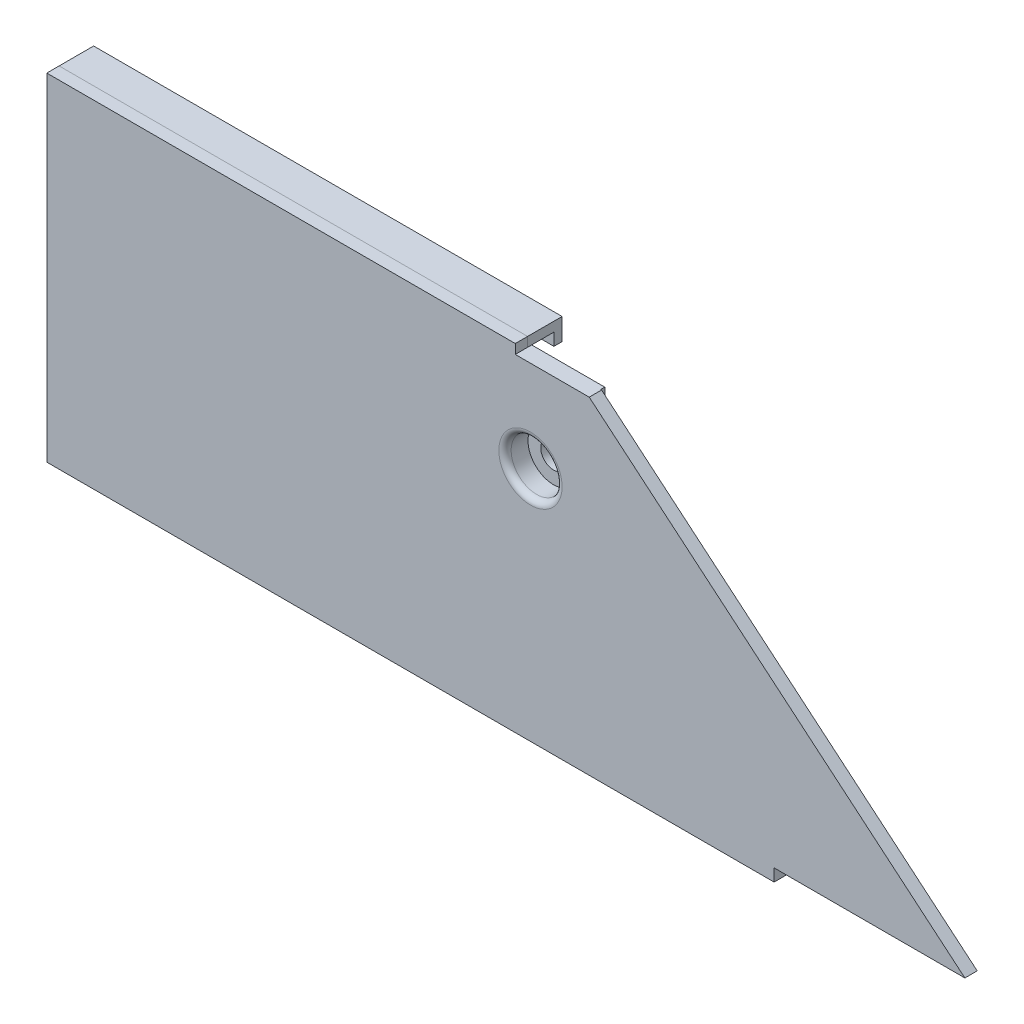
SolidWorks part; units mm, degrees
ref_plane "Спереди" through (0, 0, 0) normal (0, 0, 1) x (1, 0, 0)
ref_plane "Сверху" through (0, 0, 0) normal (0, 1, 0) x (1, 0, 0)
ref_plane "Справа" through (0, 0, 0) normal (1, 0, 0) x (0, 0, -1)
sketch "Эскиз2" plane through (0, 0, 0) normal (0, 0, 1) x (1, 0, 0)
  line L0 (-45.1615, 41.0019) -> (-45.1615, 31.0019) construction
  line L1 (-45.1615, 31.0019) -> (-100.1615, 31.0019) construction
  line L2 (-46.6615, 41.0019) -> (-46.6615, 32.1019) construction
  line L3 (-46.6615, 32.1019) -> (-100.1615, 32.1019) construction
  line L4 (-46.6615, 30.6019) -> (-45.1615, 30.6019) construction
  line L5 (-45.1615, 30.6019) -> (-45.1615, 31.0019) construction
  line L6 (-45.1615, 31.0019) -> (-46.6615, 31.0019) construction
  line L7 (-46.6615, 31.0019) -> (-46.6615, 30.6019) construction
  line L8 (-13.6668, 0) -> (13.6668, 0) construction
  line L9 (13.6668, 0) -> (-35.1974, 41.0019) construction
  line L10 (-35.1974, 41.0019) -> (-45.1615, 41.0019) construction
  line L11 (-13.6668, 0) -> (-13.6668, 1.5)
  line L12 (-13.6668, 1.5) -> (9.5456, 1.5)
  line L13 (-45.1615, 41.0019) -> (-45.1615, 39.8528)
  line L14 (9.5456, 1.5) -> (-36.1615, 39.8528)
  line L15 (-45.1615, 39.8528) -> (-36.1615, 39.8528)
  line L16 (-45.1615, 41.0019) -> (-100.1615, 41.0019)
  line L17 (-100.1615, 41.0019) -> (-100.1615, 0) construction
  line L18 (-100.1615, 0) -> (-13.6668, 0)
  line L20 (-39.9615, 25.4019) -> (-46.6615, 25.4019) construction
  line L21 (-39.9615, 25.4019) -> (-39.9615, 32.1019) construction
  line L22 (-39.9615, 32.1019) -> (-46.6615, 32.1019) construction
  line L23 (-46.6615, 25.4019) -> (-46.6615, 32.1019) construction
  line L24 (-100.1615, 0) -> (-102.1615, 0)
  line L25 (-100.1615, 0) -> (-100.1615, 41.0019) construction
  line L26 (-100.1615, 41.0019) -> (-102.1615, 41.0019)
  line L27 (-102.1615, 0) -> (-102.1615, 41.0019)
  circle A0 centre (-43.3115, 28.7519) radius 1.55
  point P0 (-45.1615, 31.0019)
  point P1 (-46.6615, 41.0019)
  point P4 (-46.6615, 32.1019)
  point P7 (-100.1615, 22.1019)
  point P12 (0, 0)
  point P13 (12.7026, -1.1491)
  point P19 (-43.3115, 28.7519)
  point P24 (-43.1115, 30.7362)
  point P25 (-44.6615, 29.1862)
  point P26 (-46.6615, 30.6019)
  point P27 (-45.1615, 30.6019)
  point P32 (-39.9615, 28.7519)
  point P33 (-43.3115, 25.4019)
  point P34 (-39.9615, 25.4019)
  dimension "D7" = 1.85
  dimension "D15" = 3.1
  dimension "D2" = 10
  dimension "D3" = 1.5
  dimension "D4" = 40
  dimension "D5" = 1.1
  dimension "D6" = 10
  dimension "D8" = 1.5
  dimension "D9" = 1.5
  dimension "D10" = 23.2124
  dimension "D11" = 27.3336
  dimension "D12" = 0
  dimension "D13" = 55
  dimension "D14" = 1.85
  dimension "D16" = 3.35
  dimension "D17" = 3.35
  dimension "D18" = 2
extrude "Бобышка-Вытянуть1" add sketch "Эскиз2" along normal blind 1.5
sketch "Эскиз3" plane through (0, 0, 0) normal (0, 0, -1) x (-1, 0, 0)
  line L1 (45.1615, 39.8528) -> (36.2715, 39.8528)
  line L2 (45.1615, 39.8528) -> (45.1615, 38.3528)
  line L3 (45.1615, 38.3528) -> (36.2715, 38.3528)
  line L4 (36.2715, 39.8528) -> (36.2715, 38.3528)
  dimension "D1" = 1.5
extrude "Бобышка-Вытянуть2" add sketch "Эскиз3" along normal blind 0.5
sketch "Эскиз4" plane through (0, 0, 0) normal (0, 0, -1) x (-1, 0, 0)
  line L1 (45.1615, 39.8528) -> (102.1615, 39.8528)
  line L2 (45.1615, 39.8528) -> (45.1615, 41.0019)
  line L3 (45.1615, 41.0019) -> (102.1615, 41.0019)
  line L4 (102.1615, 39.8528) -> (102.1615, 41.0019)
extrude "Бобышка-Вытянуть6" add sketch "Эскиз4" along normal blind 3.2 separate body
sketch "Эскиз5" plane through (0, 0, -3.2) normal (0, 0, -1) x (-1, 0, 0)
  line L1 (45.1615, 38.3528) -> (102.1615, 38.3528)
  line L2 (45.1615, 38.3528) -> (45.1615, 41.0019)
  line L3 (45.1615, 41.0019) -> (102.1615, 41.0019)
  line L4 (102.1615, 38.3528) -> (102.1615, 41.0019)
extrude "Бобышка-Вытянуть7" add sketch "Эскиз5" along normal blind 1
sketch "Эскиз6" plane through (0, 0, 0) normal (0, 0, -1) x (-1, 0, 0)
  circle A0 centre (43.3115, 28.7519) radius 3.4
  dimension "D1" = 6.8
extrude "Бобышка-Вытянуть8" add sketch "Эскиз6" along normal blind 3
sketch "Эскиз7" plane through (0, 0, 0) normal (0, 0, 1) x (1, 0, 0)
  circle A0 centre (-43.3115, 28.7519) radius 1.55
extrude "Вырез-Вытянуть1" cut sketch "Эскиз7" against normal blind 3
sketch "Эскиз8" plane through (0, 0, 1.5) normal (0, 0, 1) x (1, 0, 0)
  circle A0 centre (-43.3115, 28.7519) radius 3.1
  dimension "D1" = 6.2
extrude "Вырез-Вытянуть2" cut sketch "Эскиз8" against normal blind 2.8
fillet "Скругление1" radius 3 1 edges at (-39.9115, 28.7519, 0)
fillet "Скругление2" radius 0.75 1 edges at (-40.2115, 28.7519, 1.5)
sketch "Эскиз10" plane through (0, 0, 0) normal (0, 0, -1) x (-1, 0, 0)
  circle A1 centre (43.3115, 28.7519) radius 6.4 construction
  point P4 (36.9115, 28.7519)
